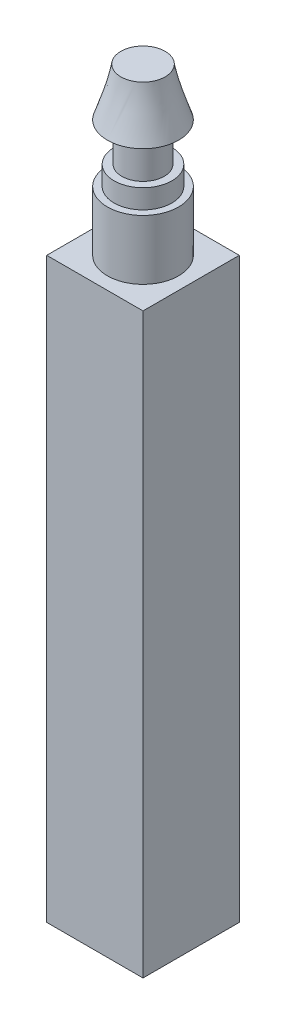
SolidWorks part; units mm, degrees
ref_plane "Front Plane" through (0, 0, 0) normal (0, 0, 1) x (1, 0, 0)
ref_plane "Top Plane" through (0, 0, 0) normal (0, 1, 0) x (1, 0, 0)
ref_plane "Right Plane" through (0, 0, 0) normal (1, 0, 0) x (0, 0, -1)
sketch "Sketch1" plane through (0, 0, 0) normal (0, 1, 0) x (1, 0, 0)
  circle A0 centre (0, 0) radius 1.85
  dimension "D1" = 3.7
extrude "Boss-Extrude1" add sketch "Sketch1" along normal blind 3.1
sketch "Sketch2" plane through (0, 3.1, 0) normal (0, 1, 0) x (1, 0, 0)
  circle A0 centre (0, 0) radius 1.5
  dimension "D1" = 3
extrude "Boss-Extrude2" add sketch "Sketch2" along normal blind 1
sketch "Sketch3" plane through (0, 4.1, 0) normal (0, 1, 0) x (1, 0, 0)
  circle A0 centre (0, 0) radius 1.1
  dimension "D1" = 2.2
extrude "Boss-Extrude3" add sketch "Sketch3" along normal blind 2
sketch "Sketch4" plane through (0, 6.1, 0) normal (0, 1, 0) x (1, 0, 0)
  circle A0 centre (0, 0) radius 1.85
  dimension "D1" = 3.7
ref_plane "Plane1" through (0, 8.6, 0) normal (0, 1, 0) x (1, 0, 0)
sketch "Sketch5" plane through (0, 8.6, 0) normal (0, 1, 0) x (1, 0, 0)
  circle A0 centre (0, 0) radius 1.15
  dimension "D1" = 2.3
loft "Loft1" add profiles "Sketch4", "Sketch5" connector at (0, 6.1, 1.85) connector at (0.6205, 8.6, 0.9683)
sketch "Sketch6" plane through (0, 0, 0) normal (0, -1, 0) x (1, 0, 0)
  line L1 (-2.5, 2.5) -> (2.5, 2.5)
  line L2 (-2.5, 2.5) -> (-2.5, -2.5)
  line L3 (-2.5, -2.5) -> (2.5, -2.5)
  line L4 (2.5, 2.5) -> (2.5, -2.5)
  line L5 (-2.5, 2.5) -> (2.5, -2.5) construction
  line L6 (-2.5, -2.5) -> (2.5, 2.5) construction
  point P0 (0, 0)
  dimension "D1" = 5
  dimension "D2" = 5
extrude "Boss-Extrude4" add sketch "Sketch6" along normal blind 30
sketch "Sketch7" plane through (0, -30, 0) normal (0, -1, 0) x (1, 0, 0)
  circle A0 centre (0, 0) radius 1
  dimension "D1" = 2
extrude "Cut-Extrude1" cut sketch "Sketch7" against normal blind 24
